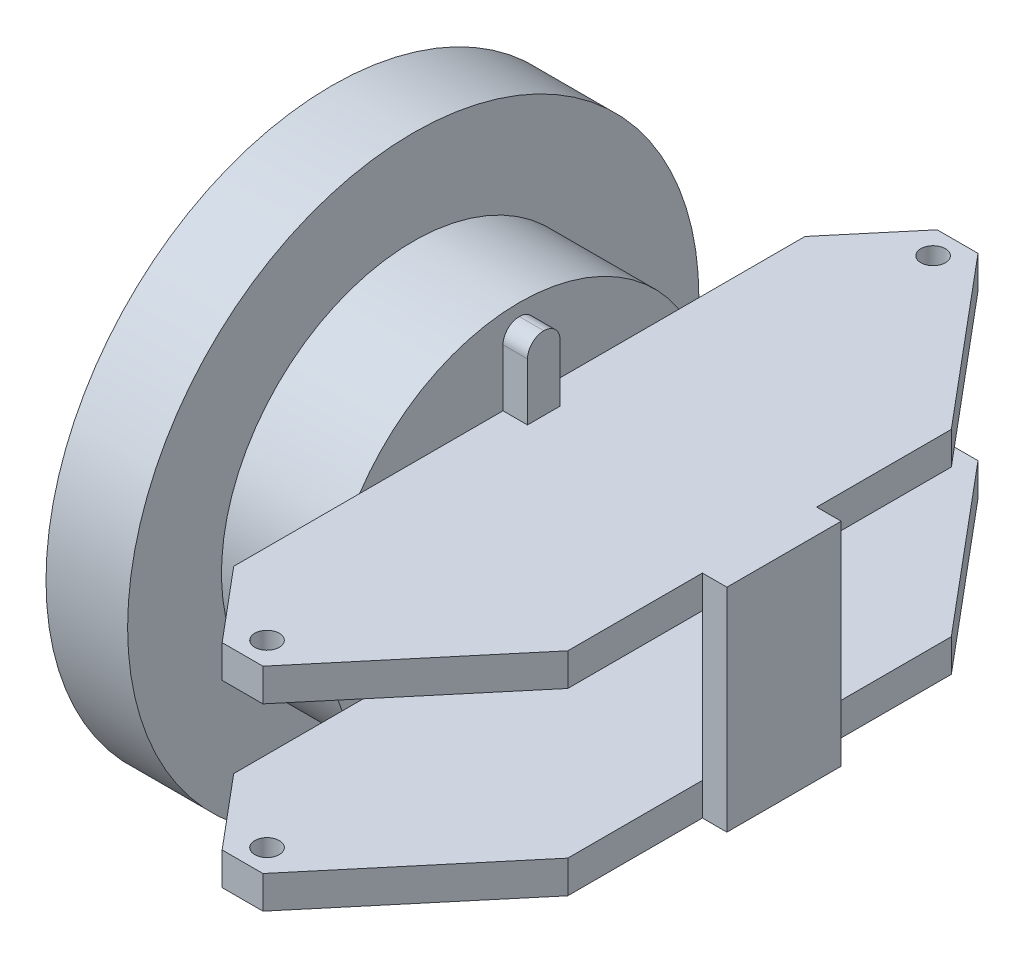
SolidWorks part; units mm, degrees
ref_plane "Front Plane" through (0, 0, 0) normal (0, 0, 1) x (1, 0, 0)
ref_plane "Top Plane" through (0, 0, 0) normal (0, 1, 0) x (1, 0, 0)
ref_plane "Right Plane" through (0, 0, 0) normal (1, 0, 0) x (0, 0, -1)
sketch "Sketch1" plane through (0, 0, 0) normal (1, 0, 0) x (0, 0, -1)
  circle A0 centre (0, 0) radius 35
  dimension "D1" = 70
extrude "Boss-Extrude1" add sketch "Sketch1" along normal blind 10
sketch "Sketch2" plane through (10, 0, 0) normal (1, 0, 0) x (0, 0, -1)
  circle A0 centre (0, 0) radius 23.5
  dimension "D1" = 47
extrude "Boss-Extrude2" add sketch "Sketch2" along normal blind 13
ref_plane "Plane1" through (0, 13, 0) normal (0, 1, 0) x (1, 0, 0)
sketch "Sketch3" plane through (0, 13, 0) normal (0, 1, 0) x (1, 0, 0)
  line L0 (23, 35) -> (23, -35)
  line L1 (23, -23.5) -> (23, 23.5) construction
  line L2 (23, -35) -> (30.3921, -43.8095)
  line L3 (30.3921, -43.8095) -> (35.3921, -43.8095)
  line L4 (35.3921, -43.8095) -> (52.4338, -23.5)
  line L5 (35.3921, -43.8095) -> (46.1178, -43.8095) construction
  line L6 (23, -23.5) -> (64.8509, -23.5) construction
  line L7 (52.4338, -23.5) -> (52.4338, 23.5)
  line L8 (23, 0) -> (51.0831, 0) construction
  line L9 (30.3921, 43.8095) -> (35.3921, 43.8095)
  line L10 (35.3921, 43.8095) -> (52.4338, 23.5)
  line L11 (23, 35) -> (30.3921, 43.8095)
  line L12 (10, -23.5) -> (23, -23.5) construction
  point P15 (52.4338, 0)
  dimension "D1" = 35
  dimension "D2" = 11.5
  dimension "D3" = 40
  dimension "D4" = 5
  dimension "D5" = 50
extrude "Boss-Extrude3" add sketch "Sketch3" against normal blind 4
sketch "Sketch4" plane through (0, 13, 0) normal (0, 1, 0) x (1, 0, 0)
  line L0 (30.3921, -43.8095) -> (35.3921, -43.8095) construction
  circle A0 centre (32.8921, -40.8095) radius 1.5
  dimension "D1" = 3
  dimension "D2" = 3
extrude "Cut-Extrude1" cut sketch "Sketch4" against normal blind 4
mirror "Mirror1" about plane through (0, 0, 0) normal (0, 0, 1) of "Cut-Extrude1"
mirror "Mirror2" about plane through (0, 0, 0) normal (0, 1, 0) of "Mirror1", "Cut-Extrude1", "Boss-Extrude3"
sketch "Sketch6" plane through (23, 0, 0) normal (1, 0, 0) x (0, 0, -1)
  line L0 (0, 13) -> (0, 23.5) construction
  line L1 (-23.5, 13) -> (23.5, 13) construction
  line L2 (-2, 13) -> (-2, 22)
  line L3 (-2, 22) -> (2, 22)
  line L4 (2, 22) -> (2, 13)
  line L5 (2, 13) -> (-2, 13)
  arc A0 (19.5768, 13) -> (-19.5768, 13) centre (0, 0) ccw construction
  dimension "D1" = 9
  dimension "D2" = 2
  dimension "D3" = 2
extrude "Boss-Extrude5" add sketch "Sketch6" along normal blind 3
fillet "Fillet1" radius 2 2 edges at (24.5, 22, -2) (24.5, 22, 2)
mirror "Mirror3" about plane through (0, 0, 0) normal (0, 1, 0) of "Boss-Extrude5", "Fillet1"
sketch "Sketch7" plane through (52.4338, 0, 0) normal (1, 0, 0) x (0, 0, -1)
  line L1 (-7, 13) -> (7, 13)
  line L2 (-7, 13) -> (-7, -13)
  line L3 (-7, -13) -> (7, -13)
  line L4 (7, 13) -> (7, -13)
  line L5 (-7, 13) -> (7, -13) construction
  line L6 (-7, -13) -> (7, 13) construction
  point P0 (0, 0)
  dimension "D1" = 26
  dimension "D2" = 14
extrude "Boss-Extrude6" add sketch "Sketch7" along normal blind 3
sketch "Sketch8" plane through (0, 0, 0) normal (-1, 0, 0) x (0, 0, 1)
  circle A0 centre (0, 0) radius 10
  dimension "D1" = 20
extrude "Cut-Extrude2" cut sketch "Sketch8" against normal blind 10
